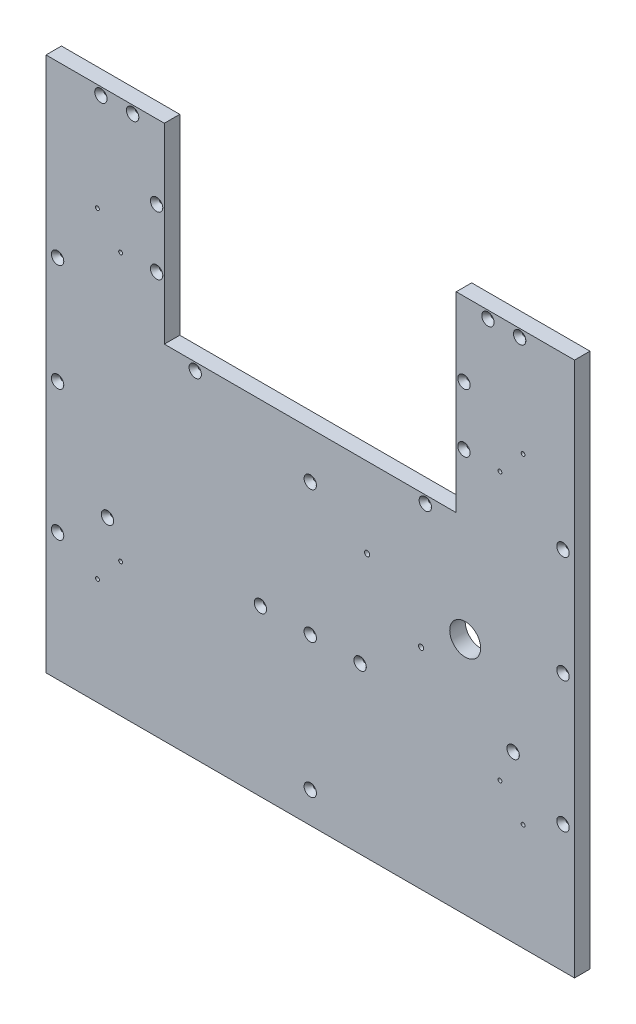
SolidWorks part; units mm, degrees
material "Beech"
ref_plane "Front Plane" through (0, 0, 0) normal (0, 0, 1) x (1, 0, 0)
ref_plane "Top Plane" through (0, 0, 0) normal (0, 1, 0) x (1, 0, 0)
ref_plane "Right Plane" through (0, 0, 0) normal (1, 0, 0) x (0, 0, -1)
sketch "Sketch1" plane through (0, 0, 0) normal (0, 0, 1) x (1, 0, 0)
  line L0 (341.3045, 12.7) -> (244.0045, 12.7)
  line L2 (341.3045, 12.7) -> (244.0045, 12.7) construction
  line L3 (244.0045, 12.7) -> (244.0045, -144.6)
  line L4 (244.0045, -144.6) -> (124.0045, -144.6)
  line L5 (341.3045, -455.5295) -> (-93.2955, -455.5295) construction
  line L6 (124.0045, -144.6) -> (124.0045, -427.3421)
  line L7 (124.0045, -427.3421) -> (341.3045, -427.3421)
  line L8 (341.3045, -427.3421) -> (341.3045, 12.7)
  line L12 (16.7045, -144.6) -> (231.3045, -144.6) construction
  point P18 (124.0045, -144.6)
  dimension "D1" = 28.1874
extrude "Boss-Extrude1" add sketch "Sketch1" along normal blind 12.7
mirror "Mirror1" about plane through (124.0045, -144.6, 12.7) normal (1, 0, 0) of "Boss-Extrude1"
hole_wizard "Hole1" positions "Sketch2" profile "Sketch3" legacy
sketch "Sketch2" plane through (124.0045, 10.4243, 12.7) normal (0, 0, 1) x (-1, 0, 0)
  line L12 (0, 0) -> (0, 155.0243) construction
  point P0 (-207.775, 333.0214)
  point P3 (-207.775, 225.489)
  point P6 (-207.775, 137.4243)
  point P9 (-172.1667, 4.0743)
  point P12 (-146.0833, 4.0743)
  point P15 (-94.6, 161.3743)
  point P21 (94.6, 161.3743)
  point P24 (146.0833, 4.0743)
  point P27 (172.1667, 4.0743)
  point P30 (207.775, 137.4243)
  point P33 (207.775, 225.489)
  point P36 (207.775, 333.0214)
  point P39 (166.7958, 301.9704)
  point P42 (40.9792, 301.9704)
  point P45 (-40.9792, 301.9704)
  point P48 (-166.7958, 301.9704)
  point P51 (0, 193.1243)
  point P54 (0, 301.9704)
  point P57 (0, 412.3664)
  point P80 (-126.35, 106.8243)
  point P82 (-126.35, 58.6243)
  point P96 (126.35, 58.6243)
  point P97 (126.35, 106.8243)
  point P99 (0, 0)
sketch "Sketch3" plane through (331.7795, -322.5971, 12.7) normal (1, 0, 0) x (0, -1, 0)
  line L0 (0, 0) -> (0, 32.7039)
  line L1 (0, 32.7039) -> (1.5875, 31.75)
  line L2 (1.5875, 31.75) -> (1.5875, 4.0177)
  line L3 (1.5875, 4.0177) -> (5.08, 0)
  line L4 (5.08, 0) -> (0, 0)
  line L5 (0, -14.3089) -> (0, 102.4216) construction
  line L6 (0, 32.7039) -> (-1.5875, 31.75) construction
  line L7 (-1.5875, 4.0177) -> (-5.08, 0) construction
  dimension "Diameter" = 3.175
  dimension "Depth" = 31.75
  dimension "C-Sink Diameter" = 10.16
  dimension "C-Sink Angle" = 82
  dimension "Drill Angle" = 118
hole_wizard "Hole2" positions "Sketch4" profile "Sketch5" legacy
sketch "Sketch4" plane through (124.0045, 10.4243, 0) normal (0, 0, -1) x (1, 0, 0)
  line L8 (155.95, -2.2757) -> (155.95, 437.7664) construction
  line L11 (175, -2.2757) -> (175, 437.7664) construction
  line L15 (155.95, -2.2757) -> (155.95, 107.7348)
  line L16 (155.95, 107.7348) -> (155.95, 217.7454)
  line L17 (155.95, 217.7454) -> (155.95, 327.7559)
  line L18 (155.95, 327.7559) -> (155.95, 437.7664)
  line L20 (175, -2.2757) -> (175, 85.7327)
  line L21 (175, 85.7327) -> (175, 173.7411)
  line L22 (175, 173.7411) -> (175, 261.7496)
  line L23 (175, 261.7496) -> (175, 349.758)
  line L24 (175, 349.758) -> (175, 437.7664)
  line L25 (0, 155.0243) -> (0, 437.7664) construction
  point P36 (155.95, 107.7348)
  point P40 (155.95, 327.7559)
  point P46 (175, 85.7327)
  point P52 (175, 349.758)
  point P77 (-175, 349.758)
  point P80 (-175, 85.7327)
  point P81 (-155.95, 327.7559)
  point P83 (-155.95, 107.7348)
sketch "Sketch5" plane through (-31.9455, -97.3105, 0) normal (1, 0, 0) x (0, 1, 0)
  line L0 (0, 0) -> (0, 32.7039)
  line L1 (0, 32.7039) -> (1.5875, 31.75)
  line L2 (1.5875, 31.75) -> (1.5875, 4.0177)
  line L3 (1.5875, 4.0177) -> (5.08, 0)
  line L4 (5.08, 0) -> (0, 0)
  line L5 (0, -14.3089) -> (0, 102.4216) construction
  line L6 (0, 32.7039) -> (-1.5875, 31.75) construction
  line L7 (-1.5875, 4.0177) -> (-5.08, 0) construction
  dimension "Diameter" = 3.175
  dimension "Depth" = 31.75
  dimension "C-Sink Diameter" = 10.16
  dimension "C-Sink Angle" = 82
  dimension "Drill Angle" = 118
hole_wizard "1 (1) Diameter Hole1" positions "Sketch6" profile "Sketch7" hole size "1" standard "ANSI Inch" end condition up to next
sketch "Sketch6" plane through (0, 0, 0) normal (0, 0, -1) x (-1, 0, 0)
  line L0 (-270.4295, -231.122) -> (-251.3795, -231.122) construction
  point P0 (-251.3795, -231.122)
  dimension "D1" = 19.05
sketch "Sketch7" plane through (251.3795, -231.122, 0) normal (1, 0, 0) x (0, 1, 0)
  line L0 (0, 0) -> (0, 12.7)
  line L1 (0, 12.7) -> (12.7, 12.7)
  line L2 (12.7, 12.7) -> (12.7, 0)
  line L5 (12.7, 0) -> (0, 0)
  line L11 (0, -6.35) -> (0, 107.95) construction
  dimension "Thru Hole Dia." = 25.4
  dimension "Thru Hole Depth" = 12.7
hole_wizard "#6 Clearance Hole1" positions "Sketch8" profile "Sketch9" hole size "#6" standard "ANSI Inch" end condition up to next
sketch "Sketch8" plane through (0, 0, 0) normal (0, 0, -1) x (-1, 0, 0)
  point P0 (-215.1525, -254.8561)
  point P2 (-170.7025, -210.4061)
sketch "Sketch9" plane through (215.1525, -254.8561, 0) normal (1, 0, 0) x (0, 1, 0)
  line L0 (0, 0) -> (0, 12.7)
  line L1 (0, 12.7) -> (2.1526, 12.7)
  line L2 (2.1526, 12.7) -> (2.1526, 0)
  line L5 (2.1526, 0) -> (0, 0)
  line L11 (0, -6.35) -> (0, 107.95) construction
  dimension "Thru Hole Dia." = 4.3053
  dimension "Thru Hole Depth" = 12.7
